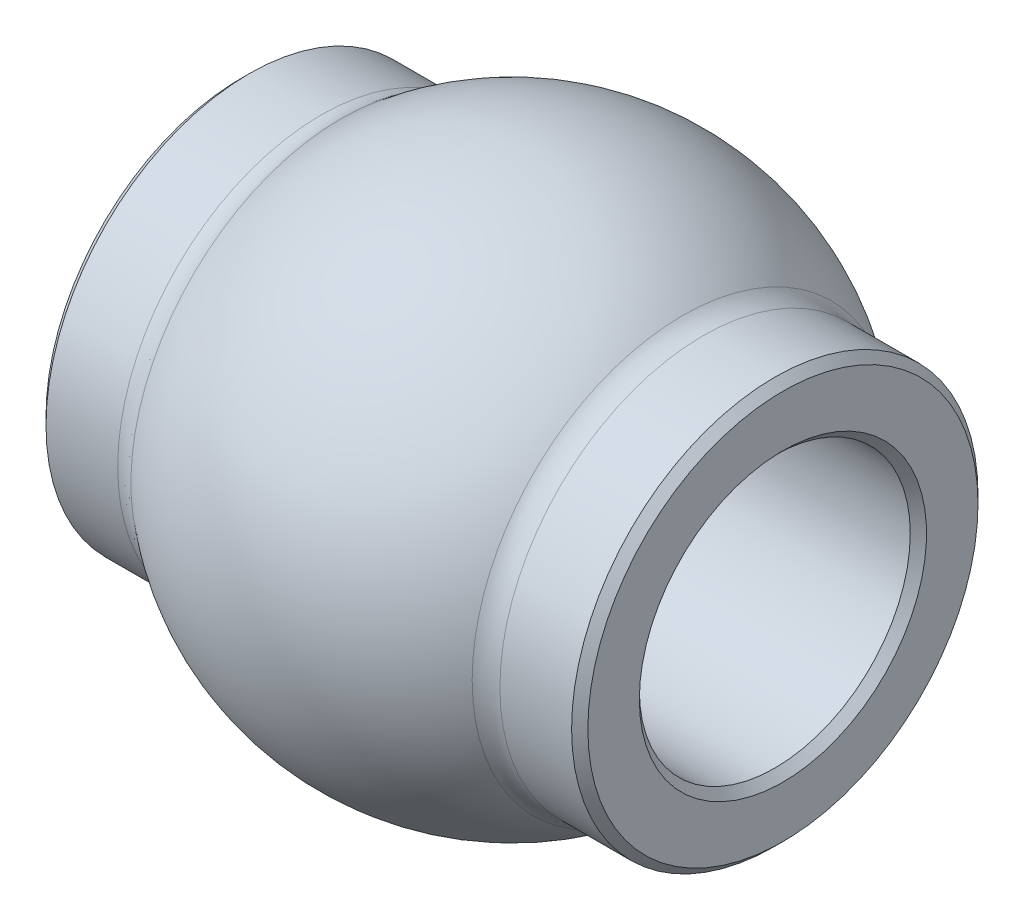
SolidWorks part; units mm, degrees
ref_plane "Front" through (0, 0, 0) normal (0, 0, 1) x (1, 0, 0)
ref_plane "Top" through (0, 0, 0) normal (0, 1, 0) x (1, 0, 0)
ref_plane "Right" through (0, 0, 0) normal (1, 0, 0) x (0, 0, -1)
sketch "Sketch1" plane through (0, 0, 0) normal (0, 0, 1) x (1, 0, 0)
  line L0 (-19.7342, 0) -> (0, 0) construction
  line L1 (0, 0) -> (0, 12.7) construction
  line L2 (-12.7, 0) -> (12.7, 0)
  line L3 (-12.7, 0) -> (-12.7, 9.525)
  line L4 (-12.7, 9.525) -> (-8.4003, 9.525)
  line L5 (12.7, 0) -> (12.7, 9.525)
  line L6 (12.7, 9.525) -> (8.4003, 9.525)
  circle A0 centre (0, 0) radius 12.7 construction
  arc A1 (-8.4003, 9.525) -> (8.4003, 9.525) centre (0, 0) cw
  point P8 (0, 0)
  dimension "D1" = 25.4
  dimension "D2" = 19.05
revolve "Revolve1" add sketch "Sketch1" angle 360 about L0
sketch "Sketch2" plane through (0, 0, 0) normal (1, 0, 0) x (0, 0, -1)
  circle A0 centre (0, 0) radius 6.35
  dimension "D1" = 12.7
extrude "Cut-Extrude1" cut sketch "Sketch2" against normal through all both and the other way through all
fillet "Fillet1" radius 1.524 2 edges at (8.4003, 0, 9.525) (-8.4003, 0, 9.525)
ref_axis "Axis1" through (23.3268, 0, 0) along (-1, 0, 0)
chamfer "Chamfer1" distance 0.381 angle 45 4 edges at (12.7, 0, 9.525) (-12.7, 0, 9.525) (12.7, 0, -6.35) (-12.7, 0, -6.35)
equation "\"diameterMajor\"= 1"
equation "\"hole_diameter\"= .5"
equation "\"sleevediameter\"= .75"
equation "\"D2@Sketch1\"=\"sleevediameter\""
equation "\"D1@Sketch2\"=\"hole_diameter\""
